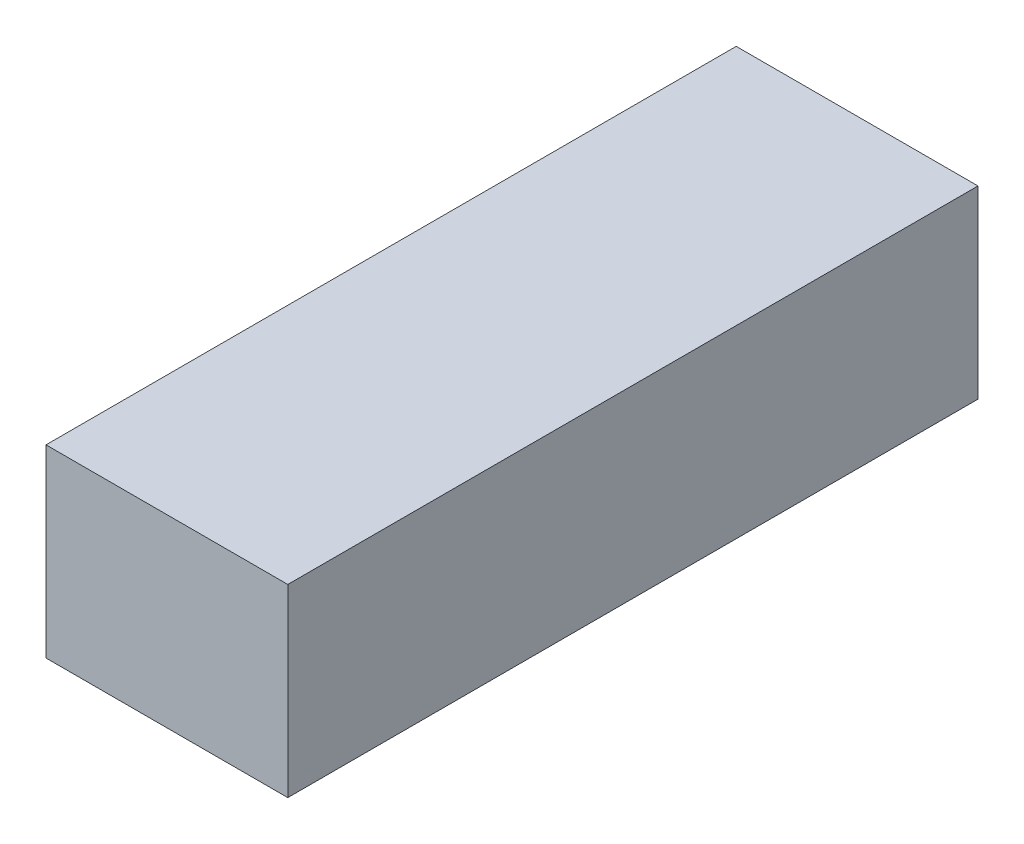
SolidWorks part; units mm, degrees
material "LiPol"
ref_plane "Płaszczyzna przednia" through (0, 0, 0) normal (0, 0, 1) x (1, 0, 0)
ref_plane "Płaszczyzna górna" through (0, 0, 0) normal (0, 1, 0) x (1, 0, 0)
ref_plane "Płaszczyzna prawa" through (0, 0, 0) normal (1, 0, 0) x (0, 0, -1)
sketch "Szkic1" plane through (0, 0, 0) normal (0, 1, 0) x (1, 0, 0)
  line L0 (0, 0) -> (0, 157)
  line L1 (0, 157) -> (55, 157)
  line L2 (55, 157) -> (55, 0)
  line L3 (55, 0) -> (0, 0)
  dimension "D1" = 157
  dimension "D2" = 55
extrude "Dodanie-wyciągnięcie1" add sketch "Szkic1" along normal blind 42
sketch "Szkic2" plane through (0, 0, 0) normal (0, 0, 1) x (1, 0, 0)
  text T0 "\r\n      Battery"
